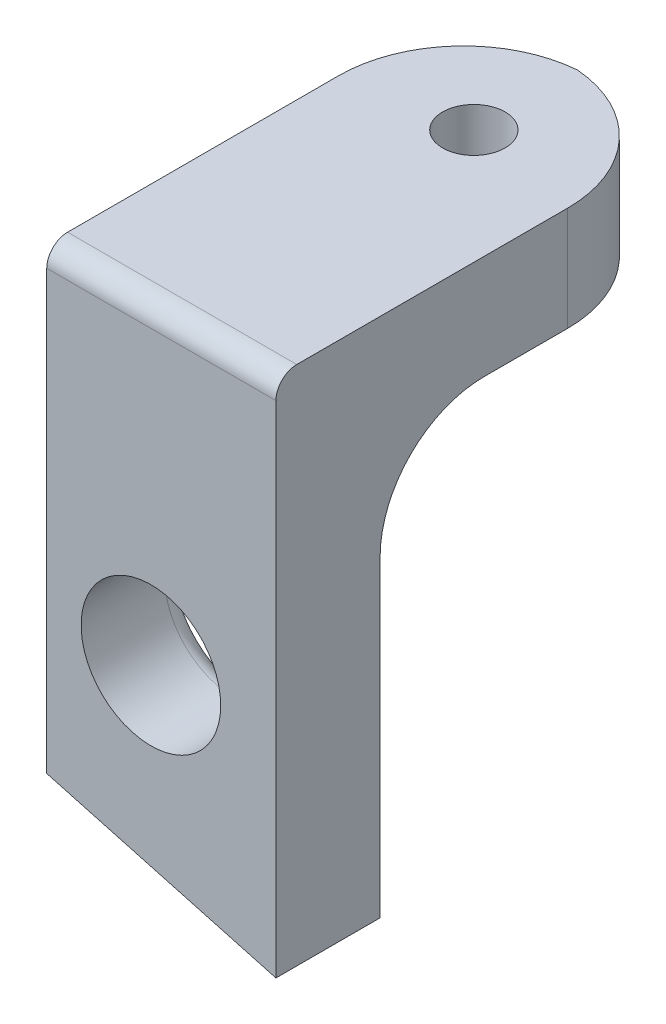
SolidWorks part; units mm, degrees
ref_plane "Спереди" through (0, 0, 0) normal (0, 0, 1) x (1, 0, 0)
ref_plane "Сверху" through (0, 0, 0) normal (0, 1, 0) x (1, 0, 0)
ref_plane "Справа" through (0, 0, 0) normal (1, 0, 0) x (0, 0, -1)
sketch "Эскиз1" plane through (0, 0, 0) normal (0, 0, 1) x (1, 0, 0)
  line L1 (-5, 10) -> (6, 10)
  line L2 (-5, 10) -> (-5, -7)
  line L3 (-5, -7) -> (6, -10)
  line L4 (6, 10) -> (6, -10)
  circle A0 centre (0, 0) radius 3.35
  dimension "D1" = 6.7
  dimension "D2" = 11
  dimension "D3" = 6
  dimension "D4" = 10
  dimension "D5" = 3
  dimension "D6" = 20
extrude "Бобышка-Вытянуть1" add sketch "Эскиз1" along normal blind 5
sketch "Эскиз2" plane through (0, 10, 0) normal (0, 1, 0) x (1, 0, 0)
  line L1 (-5, -5) -> (6, -5)
  line L2 (-5, -5) -> (-5, 15)
  line L3 (-5, 15) -> (6, 15)
  line L4 (6, -5) -> (6, 15)
  dimension "D1" = 11
  dimension "D2" = 20
extrude "Бобышка-Вытянуть2" add sketch "Эскиз2" along normal blind 5
fillet "Скругление1" radius 5 1 edges at (0.5, 10, 0)
fillet "Скругление2" radius 1 1 edges at (3.35, 0, 0)
fillet "Скругление4" radius 1 1 edges at (0.5, 15, 5)
sketch "Эскиз3" plane through (0, 10, 0) normal (0, -1, 0) x (1, 0, 0)
  line L0 (0.5, -15) -> (0.5, -5) construction
  line L1 (-0.6547, -12) -> (1.6547, -12)
  line L2 (1.6547, -12) -> (2.8094, -10)
  line L3 (2.8094, -10) -> (1.6547, -8)
  line L4 (1.6547, -8) -> (-0.6547, -8)
  line L5 (-0.6547, -8) -> (-1.8094, -10)
  line L6 (-1.8094, -10) -> (-0.6547, -12)
  line L7 (6, -15) -> (-5, -15) construction
  line L8 (6, -5) -> (-5, -5) construction
  circle A0 centre (0.5, -10) radius 2 construction
  point P14 (0, 0)
  dimension "D1" = 4
extrude "Вырез-Вытянуть1" cut sketch "Эскиз3" against normal blind 2.5
sketch "Эскиз4" plane through (0, 12.5, 0) normal (0, -1, 0) x (1, 0, 0)
  line L0 (0.5, -15) -> (0.5, -5) construction
  line L1 (6, -15) -> (-5, -15) construction
  line L2 (6, -5) -> (-5, -5) construction
  circle A0 centre (0.5, -10) radius 1.5
  point P8 (0, 0)
  dimension "D1" = 3
extrude "Вырез-Вытянуть2" cut sketch "Эскиз4" against normal blind 2.5
fillet "Скругление11" radius 6 2 edges at (6, 12.5, -15) (-5, 12.5, -15)
